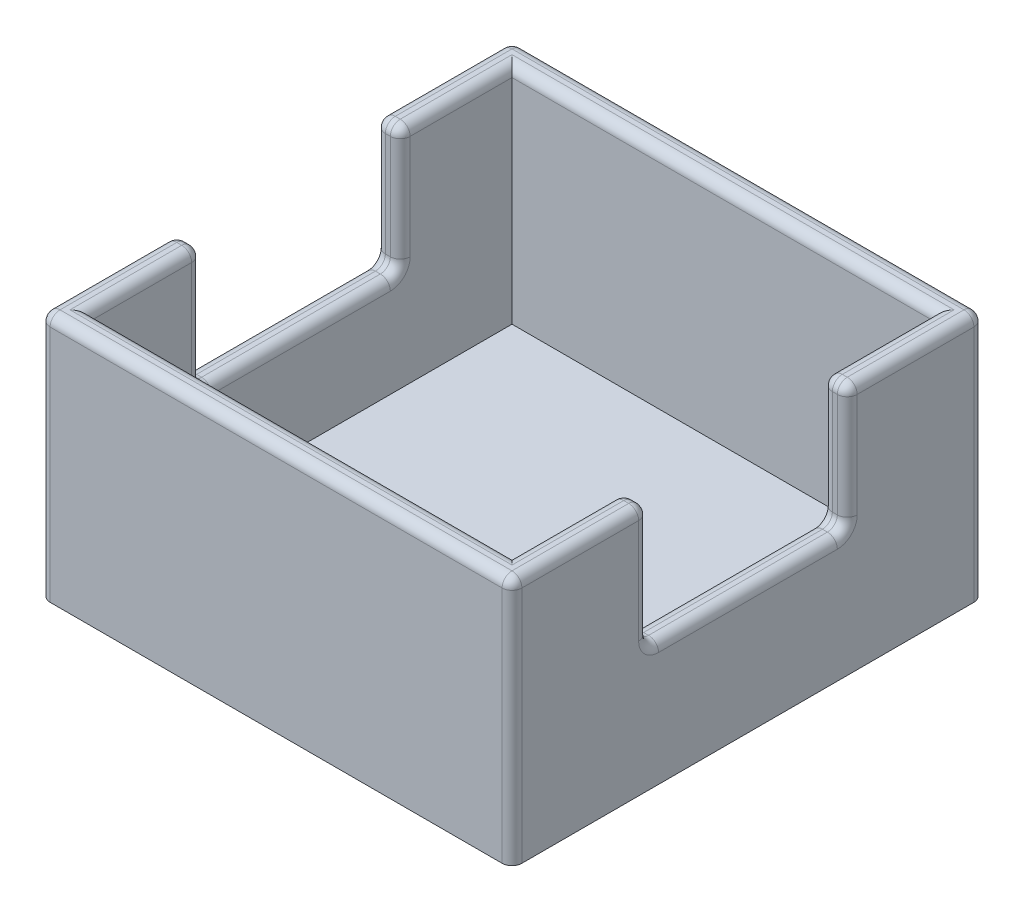
SolidWorks part; units mm, degrees
ref_plane "Front Plane" through (0, 0, 0) normal (0, 0, 1) x (1, 0, 0)
ref_plane "Top Plane" through (0, 0, 0) normal (0, 1, 0) x (1, 0, 0)
ref_plane "Right Plane" through (0, 0, 0) normal (1, 0, 0) x (0, 0, -1)
sketch "Sketch5" plane through (0, 0, 0) normal (0, 1, 0) x (1, 0, 0)
  line L1 (-47.5, -47.5) -> (47.5, -47.5)
  line L2 (-47.5, -47.5) -> (-47.5, 47.5)
  line L3 (-47.5, 47.5) -> (47.5, 47.5)
  line L4 (47.5, -47.5) -> (47.5, 47.5)
  line L5 (-47.5, -47.5) -> (47.5, 47.5) construction
  line L6 (-47.5, 47.5) -> (47.5, -47.5) construction
  point P0 (0, 0)
  dimension "D1" = 95
  dimension "D2" = 95
extrude "Boss-Extrude3" add sketch "Sketch5" along normal blind 50
shell "Shell1" thickness 5 removed face at (0, 50, 0)
sketch "Sketch6" plane through (47.5, 0, 0) normal (1, 0, 0) x (0, 0, -1)
  line L3 (-20, 75) -> (20, 75)
  line L4 (-20, 75) -> (-20, 25)
  line L5 (-20, 25) -> (20, 25)
  line L6 (20, 75) -> (20, 25)
  line L7 (-20, 75) -> (20, 25) construction
  line L8 (-20, 25) -> (20, 75) construction
  dimension "D1" = 50
  dimension "D2" = 40
extrude "Cut-Extrude2" cut sketch "Sketch6" against normal blind 100
fillet "Fillet2" radius 2 36 edges at (42.5, 37.5, -20) (47.5, 37.5, -20) (47.5, 37.5, 20) (42.5, 37.5, 20) (-47.5, 37.5, 20) (-47.5, 37.5, -20) (-42.5, 37.5, -20) (-42.5, 37.5, 20) (45, 25, -20) (47.5, 25, 0) (45, 25, 20) (42.5, 25, 0) (-47.5, 25, 0) (-45, 25, -20) (-42.5, 25, 0) (-45, 25, 20) (0, 50, 47.5) (-47.5, 50, 33.75) (-45, 50, 20) (-42.5, 50, 31.25) (0, 50, 42.5) (42.5, 50, 31.25) (45, 50, 20) (47.5, 50, 33.75) (0, 50, -47.5) (47.5, 50, -33.75) (45, 50, -20) (42.5, 50, -31.25) (0, 50, -42.5) (-42.5, 50, -31.25) (-45, 50, -20) (-47.5, 50, -33.75) (47.5, 25, -47.5) (-47.5, 25, -47.5) (47.5, 25, 47.5) (-47.5, 25, 47.5)
